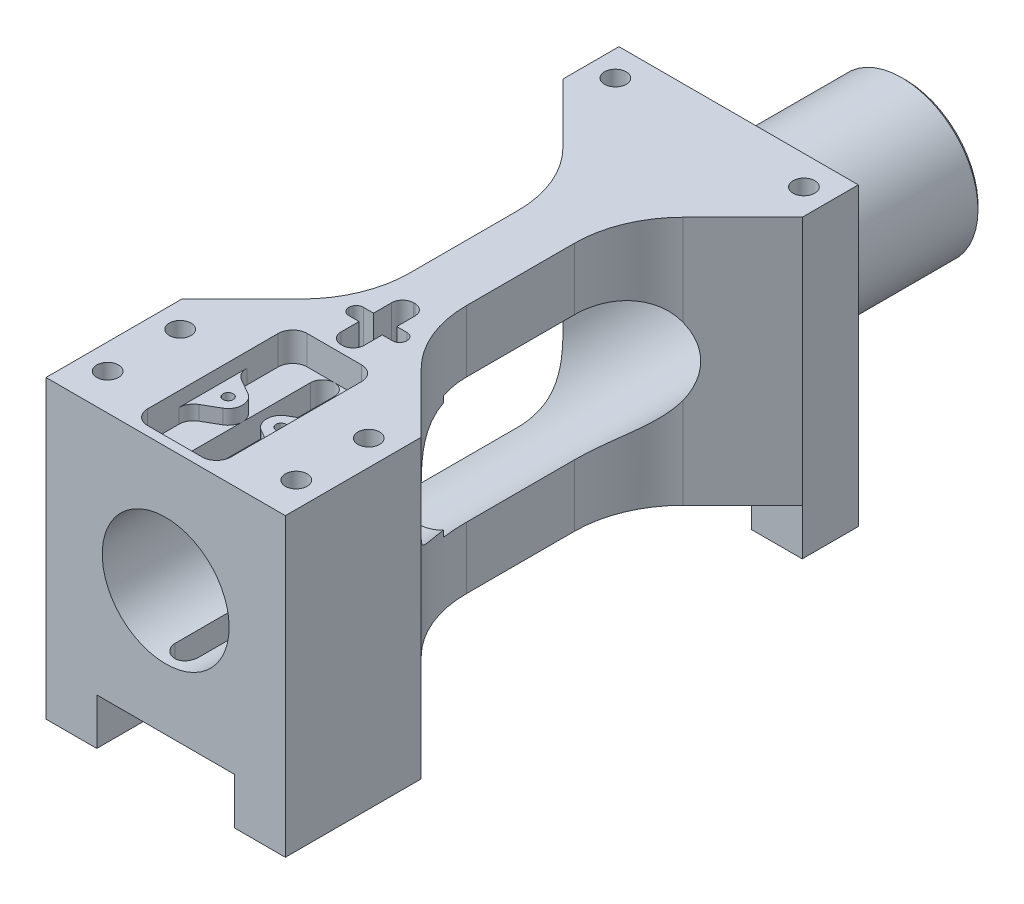
SolidWorks part; units mm, degrees
material "6061 合金"
ref_plane "前视基准面" through (0, 0, 0) normal (0, 0, 1) x (1, 0, 0)
ref_plane "上视基准面" through (0, 0, 0) normal (0, 1, 0) x (1, 0, 0)
ref_plane "右视基准面" through (0, 0, 0) normal (1, 0, 0) x (0, 0, -1)
sketch "草图1" plane through (0, 0, 0) normal (0, 1, 0) x (1, 0, 0)
  line L0 (0, 0) -> (0, 79) construction
  line L1 (-16.5, 79) -> (16.5, 79)
  line L2 (-6.9, 45) -> (-3.9, 45) construction
  line L3 (-9.5, 79) -> (-9.5, 0) construction
  line L4 (9.5, 79) -> (9.5, 0) construction
  line L5 (-16.5, 79) -> (-16.5, 71.269)
  line L6 (-16.5, 18.731) -> (-16.5, 0)
  line L7 (-16.5, 0) -> (16.5, 0)
  line L8 (-3.9, 58.669) -> (-3.9, 31.331)
  line L9 (-3.9, 31.331) -> (-16.5, 18.731)
  line L10 (-36.9, 45) -> (-15.6868, 23.7868) construction
  line L11 (-3.9, 58.669) -> (-16.5, 71.269)
  line L12 (-15.6868, 23.7868) -> (-13.5655, 21.6655) construction
  line L13 (-13, 79) -> (-13, 67.769) construction
  line L14 (-14.5, 75) -> (-14.5, 15) construction
  line L15 (16.5, 18.731) -> (16.5, 0)
  line L16 (3.9, 31.331) -> (16.5, 18.731)
  line L17 (3.9, 58.669) -> (3.9, 31.331)
  line L18 (3.9, 58.669) -> (16.5, 71.269)
  line L19 (16.5, 79) -> (16.5, 71.269)
  line L20 (-6.9, 45) -> (-14.5, 45) construction
  line L21 (-13, 15) -> (-13, 5) construction
  circle A0 centre (-36.9, 45) radius 30 construction
  circle A1 centre (36.9, 45) radius 30 construction
  circle A2 centre (-13, 75) radius 1.5
  circle A5 centre (13, 75) radius 1.5
  circle A6 centre (13, 15) radius 1.5
  circle A7 centre (-13, 15) radius 1.5
  circle A8 centre (-13, 5) radius 1.5
  circle A9 centre (13, 5) radius 1.5
  point P5 (0, 79)
  dimension "D1" = 60
  dimension "D7" = 3
  dimension "D11" = 2
  dimension "D12" = 60
  dimension "D9" = 15
  dimension "D13" = 5
  dimension "D2" = 73.8
  dimension "D3" = 19
  dimension "D4" = 3
  dimension "D5" = 45
  dimension "D6" = 7
  dimension "D8" = 4
  dimension "D10" = 3.5
extrude "凸台-拉伸1" add sketch "草图1" along normal blind 40.8
ref_plane "基准面1" through (0, 23.6, 0) normal (0, -1, 0) x (-1, 0, 0)
fillet "圆角1" radius 15 4 edges at (-3.9, 20.4, -58.669) (-3.9, 20.4, -31.331) (3.9, 20.4, -58.669) (3.9, 20.4, -31.331)
sketch "草图2" plane through (0, 23.6, 0) normal (0, -1, 0) x (-1, 0, 0)
  line L0 (0, 79) -> (0, 0) construction
  line L1 (-16.5, 79) -> (16.5, 79) construction
  line L2 (3.9, 45) -> (36.9, 45) construction
  line L3 (3.9, 52.4558) -> (3.9, 37.5442) construction
  line L4 (-8.75, 34.0164) -> (-8.75, 0)
  line L5 (16.5, 0) -> (-16.5, 0) construction
  line L6 (-8.75, 0) -> (0, 0)
  line L7 (0, 0) -> (0, 79)
  line L8 (0, 79) -> (-9.5, 79)
  line L9 (-9.5, 79) -> (-9.5, 34.0164)
  line L10 (-9.5, 34.0164) -> (-8.75, 34.0164)
  line L11 (-8.75, 34.0164) -> (-8.5, 34.0164) construction
  circle A0 centre (36.9, 45) radius 30 construction
  circle A1 centre (-36.9, 45) radius 30 construction
  circle A2 centre (0, 34.0164) radius 8.5 construction
  dimension "D1" = 60
  dimension "D2" = 73.8
  dimension "D3" = 17
  dimension "D4" = 9.5
  dimension "D5" = 8.75
revolve "切除-旋转1" cut sketch "草图2" angle 360 about L7
sketch "草图3" plane through (0, 0, 0) normal (1, 0, 0) x (0, 0, -1)
  line L0 (26.481, 23.6) -> (64.269, 23.6) construction
  line L1 (26.481, 23.6) -> (0, 23.6) construction
  line L2 (0, 40.8) -> (0, 0) construction
  line L3 (45.375, 23.6) -> (45.375, 60.5) construction
  line L4 (29.261, 31.65) -> (29.261, 15.55) construction
  line L5 (37.5442, 40.8) -> (26.9376, 40.8) construction
  line L6 (28.261, 40.8) -> (30.261, 40.8)
  line L7 (34.0164, 23.6) -> (34.0164, 31.2088) construction
  line L8 (28.261, 40.8) -> (28.261, 34.15)
  line L9 (28.261, 34.15) -> (30.261, 34.15)
  line L10 (0, 32.35) -> (45.375, 32.35) construction
  line L11 (0, 14.85) -> (45.375, 14.85) construction
  line L12 (30.261, 40.8) -> (30.261, 34.15)
  line L14 (28.261, 13.05) -> (30.261, 13.05)
  line L15 (28.261, 13.05) -> (28.261, 0)
  line L16 (28.261, 0) -> (30.261, 0)
  line L17 (30.261, 13.05) -> (30.261, 0)
  line L18 (26.9376, 0) -> (37.5442, 0) construction
  arc A0 (26.9376, 26.3896) -> (26.9376, 20.8104) centre (35.231, 23.6) ccw construction
  arc A1 (63.0624, 18.9665) -> (63.0624, 28.2335) centre (54.769, 23.6) ccw construction
  circle A4 centre (34.0164, 23.6) radius 8.5 construction
  circle A5 centre (17.0164, 23.6) radius 8.5 construction
  circle A6 centre (29.261, 35.15) radius 3.5 construction
  circle A11 centre (45.375, 60.5) radius 30 construction
  circle A12 centre (45.375, -13.3) radius 30 construction
  circle A13 centre (29.261, 12.05) radius 3.5 construction
  circle A14 centre (29.261, 35.15) radius 1
  circle A15 centre (29.261, 12.05) radius 1
  circle A16 centre (32.5164, 23.6) radius 8.5 construction
  dimension "D1" = 17
  dimension "D2" = 7
  dimension "D3" = 16.1
  dimension "D4" = 2
  dimension "D15" = 73.8
  dimension "D16" = 60
  dimension "D5" = 1.5
  dimension "D10" = 17.5
sketch "草图6" plane through (0, 40.8, 0) normal (0, 1, 0) x (1, 0, 0)
  line L0 (0, 79) -> (0, 0) construction
  line L1 (16.5, 79) -> (-16.5, 79) construction
extrude "切除-拉伸1" cut sketch "草图3" against normal mid plane 8 contours L17 L16 L15 L14 | L12 L9 L8 L6
sketch "草图7" plane through (0, 0, 0) normal (1, 0, 0) x (0, 0, -1)
  line L0 (24.261, 40.8) -> (24.261, 0)
  line L1 (79, 40.8) -> (0, 40.8) construction
  line L2 (18.731, 0) -> (26.9376, 0) construction
  line L3 (24.261, 0) -> (34.261, 0)
  line L4 (37.5442, 0) -> (52.4558, 0) construction
  line L5 (34.261, 0) -> (34.261, 40.8)
  line L6 (34.261, 40.8) -> (24.261, 40.8)
  line L7 (29.261, 40.8) -> (29.261, 35.15) construction
  dimension "D1" = 10
extrude "切除-拉伸2" cut sketch "草图7" against normal mid plane 3.2
fillet "圆角2" radius 1.5 8 edges at (1.6, 36.5012, -24.261) (-1.6, 36.8821, -34.261) (1.6, 36.8821, -34.261) (-1.6, 36.5012, -24.261) (-1.6, 7.1179, -34.261) (1.6, 7.1179, -34.261) (1.6, 7.4988, -24.261) (-1.6, 7.4988, -24.261)
sketch "草图9" plane through (0, 40.8, 0) normal (0, 1, 0) x (1, 0, 0)
  line L0 (0, 0) -> (0, 79) construction
  line L1 (16.5, 79) -> (-16.5, 79) construction
  line L2 (-5.75, 12.261) -> (0, 12.261) construction
  line L3 (-5.75, 23.261) -> (5.75, 23.261)
  line L4 (-5.75, 23.261) -> (-5.75, 1.261)
  line L5 (-5.75, 1.261) -> (5.75, 1.261)
  line L6 (5.75, 23.261) -> (5.75, 1.261)
  line L7 (-5.75, 15.7828) -> (-2.65, 13.993)
  line L8 (-5.75, 8.7392) -> (-2.65, 10.5289)
  line L9 (5.75, 8.7392) -> (2.65, 10.5289)
  line L10 (5.75, 15.7828) -> (2.65, 13.993)
  line L11 (0, 21.611) -> (0, 2.911) construction
  line L12 (1.65, 21.611) -> (1.65, 2.911)
  line L13 (-1.65, 21.611) -> (-1.65, 2.911)
  circle A0 centre (-3.65, 12.261) radius 0.7
  circle A1 centre (3.65, 12.261) radius 0.7
  arc A2 (-2.65, 13.993) -> (-2.65, 10.5289) centre (-3.65, 12.261) cw
  arc A3 (2.65, 13.993) -> (2.65, 10.5289) centre (3.65, 12.261) ccw
  arc A4 (1.65, 21.611) -> (-1.65, 21.611) centre (0, 21.611) ccw
  arc A5 (-1.65, 2.911) -> (1.65, 2.911) centre (0, 2.911) ccw
  point P9 (0, 23.261)
  point P22 (0, 12.261)
  dimension "D4" = 1.4
  dimension "D5" = 7.3
  dimension "D6" = 2
  dimension "D1" = 11.5
  dimension "D2" = 22
  dimension "D3" = 1
  dimension "D7" = 60
extrude "切除-拉伸5" cut sketch "草图9" against normal through all contours A5 L12 A4 L13 region at (0, 40.8, -12.261)
extrude "切除-拉伸6" cut sketch "草图9<4>" against normal blind 4 contours A4 L3 L4 L7 A2 L13 | A4 L12 A3 L10 L6 L3 | A5 L13 A2 L8 L4 L5 | A5 L5 L6 L9 A3 L12 region at (-3.5589, 40.8, -18.9342) region at (3.5589, 40.8, -18.9342) region at (-3.5589, 40.8, -5.5878) region at (3.5589, 40.8, -5.5878)
sketch "草图9<4>" plane through (0, 40.8, 0) normal (0, 1, 0) x (1, 0, 0) same geometry as "草图9"
extrude "切除-拉伸7" cut sketch "草图9<5>" against normal offset from surface (2 mm away) 2 contours A2 L7 L4 L8 A0 | L10 A3 L9 L6 A1 region at (-4.2408, 40.8, -14.8174) region at (5.6685, 40.8, -12.261) up to face at (2.9266, 36.8, -6.0811)
sketch "草图9<5>" plane through (0, 40.8, 0) normal (0, 1, 0) x (1, 0, 0) same geometry as "草图9"
extrude "切除-拉伸8" cut sketch "草图9<6>" against normal up to surface (4 mm away) contours A0 | A1 up to face at (2.9266, 36.8, -18.4409)
sketch "草图9<6>" plane through (0, 40.8, 0) normal (0, 1, 0) x (1, 0, 0) same geometry as "草图9"
fillet "圆角3" radius 2 8 edges at (5.75, 37.8, -15.7828) (5.75, 37.8, -8.7392) (-5.75, 38.8, -1.261) (5.75, 38.8, -23.261) (-5.75, 37.8, -8.7392) (-5.75, 37.8, -15.7828) (-5.75, 38.8, -23.261) (5.75, 38.8, -1.261)
sketch "草图10" plane through (0, 0, 0) normal (0, -1, 0) x (1, 0, 0)
  line L0 (5.75, -3.261) -> (5.75, -7.5845) construction
  line L1 (4.75, -9.3165) -> (2.65, -10.5289) construction
  line L2 (1.65, -12.261) -> (1.65, -2.911) construction
  line L3 (0, -1.261) -> (3.75, -1.261) construction
  line L4 (4.75, -15.2055) -> (2.65, -13.993) construction
  line L5 (2.65, -10.5289) -> (4.75, -9.3165) construction
  line L6 (5.75, -7.5845) -> (5.75, -16.9375) construction
  line L7 (2.65, -13.993) -> (4.75, -15.2055) construction
  line L8 (5.75, -16.9375) -> (5.75, -21.261) construction
  line L9 (3.75, -23.261) -> (0, -23.261) construction
  line L10 (1.65, -21.611) -> (1.65, -12.261) construction
  line L11 (-5.75, -21.261) -> (-5.75, -16.9375) construction
  line L12 (-4.75, -15.2055) -> (-2.65, -13.993) construction
  line L13 (-1.65, -12.261) -> (-1.65, -21.611) construction
  line L14 (0, -23.261) -> (-3.75, -23.261) construction
  line L15 (-4.75, -9.3165) -> (-2.65, -10.5289) construction
  line L16 (-2.65, -13.993) -> (-4.75, -15.2055) construction
  line L17 (-5.75, -16.9375) -> (-5.75, -7.5845) construction
  line L18 (-5.75, -7.5845) -> (-5.75, -3.261) construction
  line L19 (-3.75, -1.261) -> (0, -1.261) construction
  line L20 (-1.65, -2.911) -> (-1.65, -12.261) construction
  line L21 (-2.65, -10.5289) -> (-4.75, -9.3165) construction
  line L22 (5.75, -3.261) -> (5.75, -7.5845)
  line L23 (4.75, -9.3165) -> (2.65, -10.5289)
  line L24 (1.65, -12.261) -> (1.65, -2.911)
  line L25 (0, -1.261) -> (3.75, -1.261)
  line L26 (4.75, -15.2055) -> (2.65, -13.993)
  line L27 (2.65, -10.5289) -> (4.75, -9.3165)
  line L28 (5.75, -7.5845) -> (5.75, -16.9375)
  line L29 (2.65, -13.993) -> (4.75, -15.2055)
  line L30 (5.75, -16.9375) -> (5.75, -21.261)
  line L31 (3.75, -23.261) -> (0, -23.261)
  line L32 (1.65, -21.611) -> (1.65, -12.261)
  line L33 (-5.75, -21.261) -> (-5.75, -16.9375)
  line L34 (-4.75, -15.2055) -> (-2.65, -13.993)
  line L35 (-1.65, -12.261) -> (-1.65, -21.611)
  line L36 (0, -23.261) -> (-3.75, -23.261)
  line L37 (-4.75, -9.3165) -> (-2.65, -10.5289)
  line L38 (-2.65, -13.993) -> (-4.75, -15.2055)
  line L39 (-5.75, -16.9375) -> (-5.75, -7.5845)
  line L40 (-5.75, -7.5845) -> (-5.75, -3.261)
  line L41 (-3.75, -1.261) -> (0, -1.261)
  line L42 (-1.65, -2.911) -> (-1.65, -12.261)
  line L43 (-2.65, -10.5289) -> (-4.75, -9.3165)
  arc A0 (4.75, -9.3165) -> (5.75, -7.5845) centre (3.75, -7.5845) ccw construction
  arc A1 (2.65, -10.5289) -> (1.65, -12.261) centre (3.65, -12.261) ccw construction
  arc A2 (1.65, -2.911) -> (0, -1.261) centre (0, -2.911) ccw construction
  arc A3 (5.75, -3.261) -> (3.75, -1.261) centre (3.75, -3.261) ccw construction
  arc A4 (2.65, -10.5289) -> (2.65, -13.993) centre (3.65, -12.261) ccw construction
  arc A5 (4.75, -9.3165) -> (5.75, -7.5845) centre (3.75, -7.5845) ccw construction
  arc A6 (5.75, -16.9375) -> (4.75, -15.2055) centre (3.75, -16.9375) ccw construction
  arc A7 (5.75, -16.9375) -> (4.75, -15.2055) centre (3.75, -16.9375) ccw construction
  arc A8 (3.75, -23.261) -> (5.75, -21.261) centre (3.75, -21.261) ccw construction
  arc A9 (0, -23.261) -> (1.65, -21.611) centre (0, -21.611) ccw construction
  arc A10 (1.65, -12.261) -> (2.65, -13.993) centre (3.65, -12.261) ccw construction
  arc A11 (-4.75, -15.2055) -> (-5.75, -16.9375) centre (-3.75, -16.9375) ccw construction
  arc A12 (-2.65, -13.993) -> (-1.65, -12.261) centre (-3.65, -12.261) ccw construction
  arc A13 (-1.65, -21.611) -> (0, -23.261) centre (0, -21.611) ccw construction
  arc A14 (-5.75, -21.261) -> (-3.75, -23.261) centre (-3.75, -21.261) ccw construction
  arc A15 (-2.65, -13.993) -> (-2.65, -10.5289) centre (-3.65, -12.261) ccw construction
  arc A16 (-4.75, -15.2055) -> (-5.75, -16.9375) centre (-3.75, -16.9375) ccw construction
  arc A17 (-5.75, -7.5845) -> (-4.75, -9.3165) centre (-3.75, -7.5845) ccw construction
  arc A18 (-3.75, -1.261) -> (-5.75, -3.261) centre (-3.75, -3.261) ccw construction
  arc A19 (0, -1.261) -> (-1.65, -2.911) centre (0, -2.911) ccw construction
  arc A20 (-1.65, -12.261) -> (-2.65, -10.5289) centre (-3.65, -12.261) ccw construction
  arc A21 (-5.75, -7.5845) -> (-4.75, -9.3165) centre (-3.75, -7.5845) ccw construction
  arc A22 (4.75, -9.3165) -> (5.75, -7.5845) centre (3.75, -7.5845) ccw
  arc A23 (2.65, -10.5289) -> (1.65, -12.261) centre (3.65, -12.261) ccw
  arc A24 (1.65, -2.911) -> (0, -1.261) centre (0, -2.911) ccw
  arc A25 (5.75, -3.261) -> (3.75, -1.261) centre (3.75, -3.261) ccw
  arc A26 (2.65, -10.5289) -> (2.65, -13.993) centre (3.65, -12.261) ccw
  arc A27 (4.75, -9.3165) -> (5.75, -7.5845) centre (3.75, -7.5845) ccw
  arc A28 (5.75, -16.9375) -> (4.75, -15.2055) centre (3.75, -16.9375) ccw
  arc A29 (5.75, -16.9375) -> (4.75, -15.2055) centre (3.75, -16.9375) ccw
  arc A30 (3.75, -23.261) -> (5.75, -21.261) centre (3.75, -21.261) ccw
  arc A31 (0, -23.261) -> (1.65, -21.611) centre (0, -21.611) ccw
  arc A32 (1.65, -12.261) -> (2.65, -13.993) centre (3.65, -12.261) ccw
  arc A33 (-4.75, -15.2055) -> (-5.75, -16.9375) centre (-3.75, -16.9375) ccw
  arc A34 (-2.65, -13.993) -> (-1.65, -12.261) centre (-3.65, -12.261) ccw
  arc A35 (-1.65, -21.611) -> (0, -23.261) centre (0, -21.611) ccw
  arc A36 (-5.75, -21.261) -> (-3.75, -23.261) centre (-3.75, -21.261) ccw
  arc A37 (-2.65, -13.993) -> (-2.65, -10.5289) centre (-3.65, -12.261) ccw
  arc A38 (-4.75, -15.2055) -> (-5.75, -16.9375) centre (-3.75, -16.9375) ccw
  arc A39 (-5.75, -7.5845) -> (-4.75, -9.3165) centre (-3.75, -7.5845) ccw
  arc A40 (-3.75, -1.261) -> (-5.75, -3.261) centre (-3.75, -3.261) ccw
  arc A41 (0, -1.261) -> (-1.65, -2.911) centre (0, -2.911) ccw
  arc A42 (-1.65, -12.261) -> (-2.65, -10.5289) centre (-3.65, -12.261) ccw
  arc A43 (-5.75, -7.5845) -> (-4.75, -9.3165) centre (-3.75, -7.5845) ccw
  circle A44 centre (-3.65, -12.261) radius 0.7 construction
  circle A45 centre (3.65, -12.261) radius 0.7 construction
  circle A46 centre (-3.65, -12.261) radius 0.7
  circle A47 centre (3.65, -12.261) radius 0.7
  line M1 (-1.65, -21.611) -> (-1.65, -2.911)
  arc M2 (-1.65, -2.911) -> (1.65, -2.911) centre (0, -2.911) cw
  line M3 (1.65, -2.911) -> (1.65, -21.611)
  arc M4 (1.65, -21.611) -> (-1.65, -21.611) centre (0, -21.611) cw
extrude "切除-拉伸9" cut sketch "草图10" against normal blind 11 contours L41 A40 L40 A39 L37 A37 M1 M2 | L22 A25 L25 A23 L23 A22 M2 M3 | L33 A36 L36 A34 L34 A33 M4 M1 | L31 A30 L30 A28 L26 A26 M3 M4 region at (3.5043, 0, -5.6639) region at (3.5043, 0, -18.8581) region at (-3.5043, 0, -5.6639) region at (-3.5043, 0, -18.8581)
extrude "切除-拉伸10" cut sketch "草图10<3>" against normal offset from surface (9 mm away) 2 contours A39 L39 A33 L34 A34 A37 L37 A46 | A28 L28 A22 L23 A23 A26 L26 A47 region at (5.6479, 0, -12.261) region at (-2.0064, 0, -13.2099) up to face at (-3.3382, 11, -5.9536)
sketch "草图10<3>" plane through (0, 0, 0) normal (0, -1, 0) x (1, 0, 0) same geometry as "草图10"
extrude "切除-拉伸11" cut sketch "草图10<4>" against normal up to surface (11 mm away) contours A46 | A47 up to face at (-3.3382, 11, -5.9536)
sketch "草图10<4>" plane through (0, 0, 0) normal (0, -1, 0) x (1, 0, 0) same geometry as "草图10"
sketch "草图15" plane through (0, 0, -79) normal (0, 0, -1) x (-1, 0, 0)
  circle A0 centre (0, 23.6) radius 9.5 construction
  circle A1 centre (0, 23.6) radius 9.5
  circle A2 centre (0, 23.6) radius 10.5
  dimension "D1" = 21
extrude "凸台-拉伸2" add sketch "草图15" along normal blind 23
chamfer "倒角1" distance 0.5 angle 45 1 edges at (-10.5, 23.6, -102)
sketch "草图16" plane through (0, 0, 0) normal (0, -1, 0) x (1, 0, 0)
  line L0 (-16.5, 0) -> (16.5, 0) construction
  line L1 (-9.5, 0) -> (9.5, 0)
  line L2 (-9.5, 0) -> (-9.5, -79)
  line L3 (-9.5, -79) -> (9.5, -79)
  line L4 (9.5, 0) -> (9.5, -79)
  line L5 (-10.5, -79) -> (10.5, -79) construction
  line L6 (-8.2934, -26.9376) -> (-16.5, -18.731) construction
  line L7 (-16.5, -18.731) -> (16.5, -18.731)
  line L8 (-16.5, -18.731) -> (-16.5, -71.269)
  line L9 (-16.5, -71.269) -> (16.5, -71.269)
  line L10 (16.5, -18.731) -> (16.5, -71.269)
  line L11 (8.2934, -63.0624) -> (16.5, -71.269) construction
  line L12 (16.5, -18.731) -> (8.2934, -26.9376) construction
  circle A0 centre (-13, -15) radius 1.5 construction
  point P8 (0, 0)
  line M12 (-16.5, -79) -> (16.5, -79)
  line M14 (16.5, -71.269) -> (8.2934, -63.0624)
  arc M15 (8.2934, -63.0624) -> (3.9, -52.4558) centre (18.9, -52.4558) cw
  line M16 (3.9, -52.4558) -> (3.9, -37.5442)
  arc M17 (3.9, -37.5442) -> (8.2934, -26.9376) centre (18.9, -37.5442) cw
  line M18 (8.2934, -26.9376) -> (16.5, -18.731)
  line M20 (16.5, 0) -> (-16.5, 0)
  line M22 (-16.5, -18.731) -> (-8.2934, -26.9376)
  arc M23 (-8.2934, -26.9376) -> (-3.9, -37.5442) centre (-18.9, -37.5442) cw
  line M24 (-3.9, -37.5442) -> (-3.9, -52.4558)
  arc M25 (-3.9, -52.4558) -> (-8.2934, -63.0624) centre (-18.9, -52.4558) cw
  line M26 (-8.2934, -63.0624) -> (-16.5, -71.269)
  line M27 (-1.6, -32.761) -> (-1.6, -30.261)
  arc M28 (-1.6, -25.761) -> (-0.1, -24.261) centre (-0.1, -25.761) cw
  line M29 (-0.1, -24.261) -> (0.1, -24.261)
  arc M30 (0.1, -24.261) -> (1.6, -25.761) centre (0.1, -25.761) cw
  line M31 (1.6, -25.761) -> (1.6, -28.261)
  arc M32 (1.6, -32.761) -> (0.1, -34.261) centre (0.1, -32.761) cw
  line M33 (0.1, -34.261) -> (-0.1, -34.261)
  arc M34 (-0.1, -34.261) -> (-1.6, -32.761) centre (-0.1, -32.761) cw
  arc M35 (-3.75, -23.261) -> (-5.75, -21.261) centre (-3.75, -21.261) cw
  line M36 (-5.75, -21.261) -> (-5.75, -3.261)
  arc M37 (-5.75, -3.261) -> (-3.75, -1.261) centre (-3.75, -3.261) cw
  line M38 (-3.75, -1.261) -> (3.75, -1.261)
  arc M39 (3.75, -1.261) -> (5.75, -3.261) centre (3.75, -3.261) cw
  line M40 (5.75, -3.261) -> (5.75, -21.261)
  arc M41 (5.75, -21.261) -> (3.75, -23.261) centre (3.75, -21.261) cw
  line M42 (3.75, -23.261) -> (-3.75, -23.261)
  dimension "D1" = 3.5
extrude "切除-拉伸16" cut sketch "草图16" against normal blind 6.4 contours L2 M22 M26 M25 M24 M23 | L2 L9 L4 L7 M14 M15 M16 M17 M18 M41 M42 M35 M22 M23 M24 M25 M26 M34 M27 M28 M29 M30 M31 M32 M33 | L4 M18 M17 M16 M15 M14 | L2 L7 L4 M35 M36 M37 M38 M39 M40 M41 M20 | L9 L2 L4 M12 | L7 M35 M41 M40 M39 M38 M37 M36 | L8 L9 L10 L7 region at (0, 0, -0.2668) region at (0, 0, -47.0264) region at (-6.9726, 0, -45) region at (0, 0, -10.0674) region at (6.9726, 0, -45) region at (0, 0, -75.1345)
fillet "圆角4" radius 1 8 edges at (-4, 9.725, -30.261) (-4, 9.725, -28.261) (4, 9.725, -30.261) (4, 9.725, -28.261) (4, 37.475, -30.261) (4, 37.475, -28.261) (-4, 37.475, -30.261) (-4, 37.475, -28.261)
